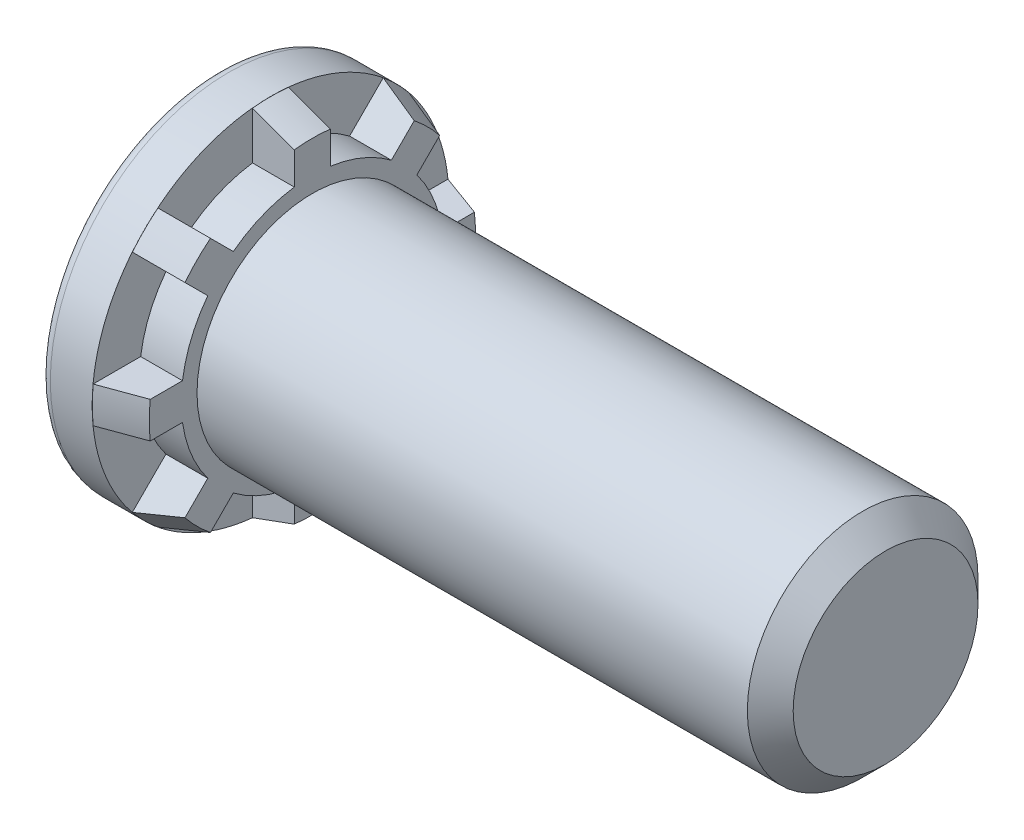
SolidWorks part; units mm, degrees
revolve "BaseBody" add sketch "BodySke" angle 360 about L6 other way angle 7.5
sketch "BodySke" plane through (0, 0, 0) normal (0, 0, 1) x (1, 0, 0)
  line L0 (-2.159, 6.9342) -> (-2.159, 0)
  line L1 (1.7272, 6.7357) -> (1.7272, 4.7625)
  line L2 (0.0025, 7.3635) -> (1.7272, 6.7357)
  line L3 (1.7272, 4.7625) -> (24.4538, 4.7625)
  line L4 (25.4, 3.8163) -> (25.4, 0)
  line L5 (25.4, 0) -> (-2.159, 0)
  line L6 (0, 0) -> (50.554, 0) construction
  line L8 (25.4, 3.8163) -> (24.4538, 4.7625)
  line L9 (-1.7272, 7.366) -> (0, 7.366)
  line L10 (0.0025, 7.3635) -> (0, 7.3635)
  line L11 (1.5875, 19.05) -> (1.5875, -3.175) construction
  line L12 (0, 7.3635) -> (0, 7.366)
  arc A0 (-2.159, 6.9342) -> (-1.7272, 7.366) centre (-1.7272, 6.9342) cw
  dimension "Fillet_rad" = 0.4318
  dimension "Minor_dia" = 7.6327
  dimension "Diameter" = 9.525
  dimension "T_dim" = 2.159
  dimension "H_dia" = 14.732
  dimension "D2" = 0.0025
  dimension "D3" = 0.0025
  dimension "Length" = 25.4
  dimension "Advance" = 1.5875
  dimension "D1" = 20
cosmetic thread "ThreadCosmetic" [suppressed] parameters "Thread_length"=21.463, "Thread_minor"=7.6327
ref_plane "Plane1" through (0, 0, 0) normal (0, 0, 1) x (1, 0, 0)
ref_plane "Plane2" through (0, 0, 0) normal (0, 1, 0) x (1, 0, 0)
ref_plane "Plane3" through (0, 0, 0) normal (1, 0, 0) x (0, 0, -1)
sketch "ThdSchSke" plane through (0, 0, 0) normal (0, 0, 1) x (1, 0, 0)
  line L0 (3.937, -3.8163) -> (3.2745, -4.7625)
  line L1 (3.937, -3.8163) -> (4.5995, -4.7625)
  line L2 (4.5995, -4.7625) -> (4.5995, -5.9531)
  line L3 (-3.175, 0) -> (5.1513, 0) construction
  line L4 (0, -7.366) -> (0, 7.366) construction
  line L5 (4.5995, -5.9531) -> (3.2745, -5.9531)
  line L6 (3.2745, -5.9531) -> (3.2745, -4.7625)
  dimension "Diameter" = 9.525
  dimension "Thread_minor" = 7.6327
  dimension "Start" = 3.937
revolve "ThreadSchematic" [suppressed] cut sketch "ThdSchSke" angle 360 about L3
pattern_linear "ThdSchPat" [suppressed]
sketch "RibCutSke" plane through (1.7272, 1.7944, -0.091) normal (1, 0, 0) x (0, 0, -1)
  line L0 (0.6541, 3.5675) -> (0.6541, 5.5338)
  line L1 (3.1736, 2.5238) -> (4.5641, 3.9142)
  line L2 (0.6541, 2.9095) -> (0.6541, 2.4006) construction
  line L3 (-0.091, -1.7944) -> (-0.091, 5.0239) construction
  line L4 (-0.091, -1.7944) -> (0.6541, 2.9095) construction
  line L5 (-0.091, -1.7944) -> (2.7084, 2.0585) construction
  line L6 (2.7084, 2.0585) -> (2.3536, 1.7038) construction
  arc A1 (3.1736, 2.5238) -> (0.6541, 3.5675) centre (-0.091, -1.7944) ccw
  arc A2 (4.5641, 3.9142) -> (0.6541, 5.5338) centre (-0.091, -1.7944) ccw
  circle A3 centre (-0.091, -1.7944) radius 6.7357 construction
  circle A4 centre (-0.091, -1.7944) radius 4.7625 construction
  dimension "Rib_root_half_angle" = 9
  dimension "Rib_root_gap_angle" = 27
  dimension "Angle" = 45
extrude "RibCut" cut sketch "RibCutSke" against normal blind 1.7272
pattern_circular "RibCutsPat" count 8 every 45 about axis through (0, 0, 0) along (1, 0, 0) of "RibCut"
equation "' \"Length@BodySke\" = 1"
equation "' \"H_dia@BodySke\" = 0.58"
equation "' \"Start@ThdSchSke\" = 0.155"
equation "' \"T_dim@BodySke\" = 0.085"
equation "' \"Diameter@BodySke\" = 0.375"
equation "' \"Minor_dia@BodySke\" = 0.3005"
equation "' \"Advance@BodySke\" = 0.0625"
equation "\"Fillet_rad@BodySke\" =  \"T_dim@BodySke\" * 0.2"
equation "\"Clinch_ht@BodySke\" = \"T_dim@BodySke\" * 0.8"
equation "\"Num_ribs@RibCutsPat\" = 8"
equation "\"Angle@RibCutSke\" =\"Angle@RibCutsPat\""
equation "\"Rib_root_half_angle@RibCutSke\" = \"Angle@RibCutSke\" / 5"
equation "\"Rib_root_gap_angle@RibCutSke\" = \"Angle@RibCutSke\" - (2 * \"Rib_root_half_angle@RibCutSke\" )"
equation "\"Rib_root_dia@RibCutSke\" = \"Diameter@BodySke\""
equation "\"Inner_dia@RibCutSke\" = \"Diameter@BodySke\" + ( \"H_dia@BodySke\" - \"Diameter@BodySke\" ) / 4"
equation "\"Outer_dia@RibCutSke\" = \"H_dia@BodySke\""
equation "\"Depth@RibCut\" = \"Clinch_ht@BodySke\""
equation "\"Thread_length@ThreadCosmetic\" = \"Length@BodySke\" - \"Start@ThdSchSke\""
equation "\"Thread_minor@ThreadCosmetic\" = \"Minor_dia@BodySke\""
equation "\"Thread_minor@ThdSchSke\" = \"Minor_dia@BodySke\""
equation "\"Diameter@ThdSchSke\" = \"Diameter@BodySke\""
equation "\"Overcut@ThdSchSke\" = \"Diameter@BodySke\" * 1.25"
equation "\"Num_threads@ThdSchPat\" = int( \"Thread_length@ThreadCosmetic\" / \"Advance@BodySke\" + 0.999 )  + 1"
equation "\"Advance@ThdSchPat\" = \"Thread_length@ThreadCosmetic\" /  (\"Num_threads@ThdSchPat\" - 1) 'relax it"
equation "\"Num_threads@ThdSchPat\" = \"Num_threads@ThdSchPat\" - sgn( \"Num_threads@ThdSchPat\" - 1) '---chamfered tips only---"
